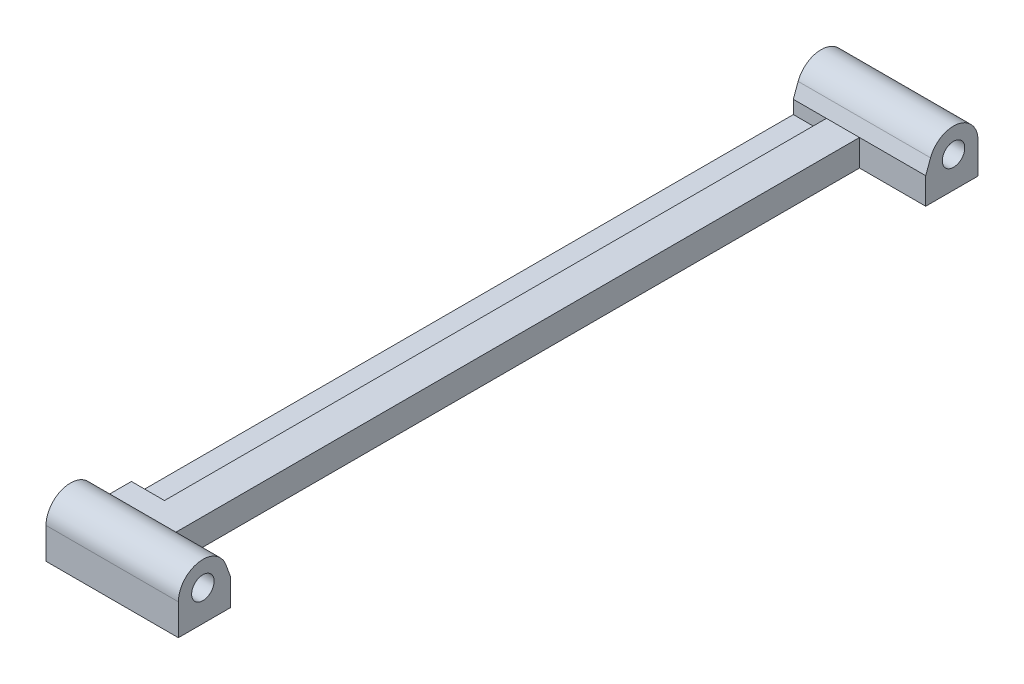
SolidWorks part; units mm, degrees
ref_plane "Plano frontal" through (0, 0, 0) normal (0, 0, 1) x (1, 0, 0)
ref_plane "Plano superior" through (0, 0, 0) normal (0, 1, 0) x (1, 0, 0)
ref_plane "Plano direito" through (0, 0, 0) normal (1, 0, 0) x (0, 0, -1)
sketch "Esboço1" plane through (0, 0, 0) normal (0, 0, 1) x (1, 0, 0)
  line L0 (0, 0) -> (0, 2)
  line L1 (0, 2) -> (5, 2)
  line L2 (5, 2) -> (5, 4)
  line L3 (5, 4) -> (10, 4)
  line L4 (10, 4) -> (10, 0)
  line L5 (10, 0) -> (0, 0)
  dimension "D1" = 2
  dimension "D2" = 2
  dimension "D3" = 5
  dimension "D4" = 5
extrude "Ressalto-extrusão1" add sketch "Esboço1" along normal blind 100
sketch "Esboço3" plane through (0, 0, 100) normal (0, 0, 1) x (1, 0, 0)
  line L1 (0, 0) -> (10, 0)
  line L2 (0, 0) -> (0, 4)
  line L3 (0, 4) -> (10, 4)
  line L4 (10, 0) -> (10, 4)
extrude "Ressalto-extrusão2" add sketch "Esboço3" along normal blind 5
sketch "Esboço4" plane through (10, 0, 0) normal (1, 0, 0) x (0, 0, -1)
  line L0 (-112.9, 4.7) -> (-112.9, 0)
  line L1 (-105.7276, 5.9775) -> (-105, 4)
  line L2 (-112.9, 0) -> (-105, 0)
  line L3 (-105, 0) -> (-105, 4) construction
  line L4 (-52.5, 0) -> (-52.5, 21.5057) construction
  line L5 (-105, 0) -> (0, 0) construction
  line L6 (7.9, 0) -> (0, 0)
  line L7 (0.7276, 5.9775) -> (0, 4)
  line L8 (7.9, 4.7) -> (7.9, 0)
  line L9 (-105, 4) -> (-105, 0)
  line L10 (0, 4) -> (0, 0)
  circle A0 centre (-109.2, 4.7) radius 1.7
  arc A1 (-112.9, 4.7) -> (-105.7276, 5.9775) centre (-109.2, 4.7) cw
  arc A2 (7.9, 4.7) -> (0.7276, 5.9775) centre (4.2, 4.7) ccw
  circle A3 centre (4.2, 4.7) radius 1.7
  dimension "D1" = 3.4
  dimension "D2" = 2
  dimension "D3" = 2.5
  dimension "D4" = 3
extrude "Ressalto-extrusão3" add sketch "Esboço4" against normal through all and the other way blind 10
